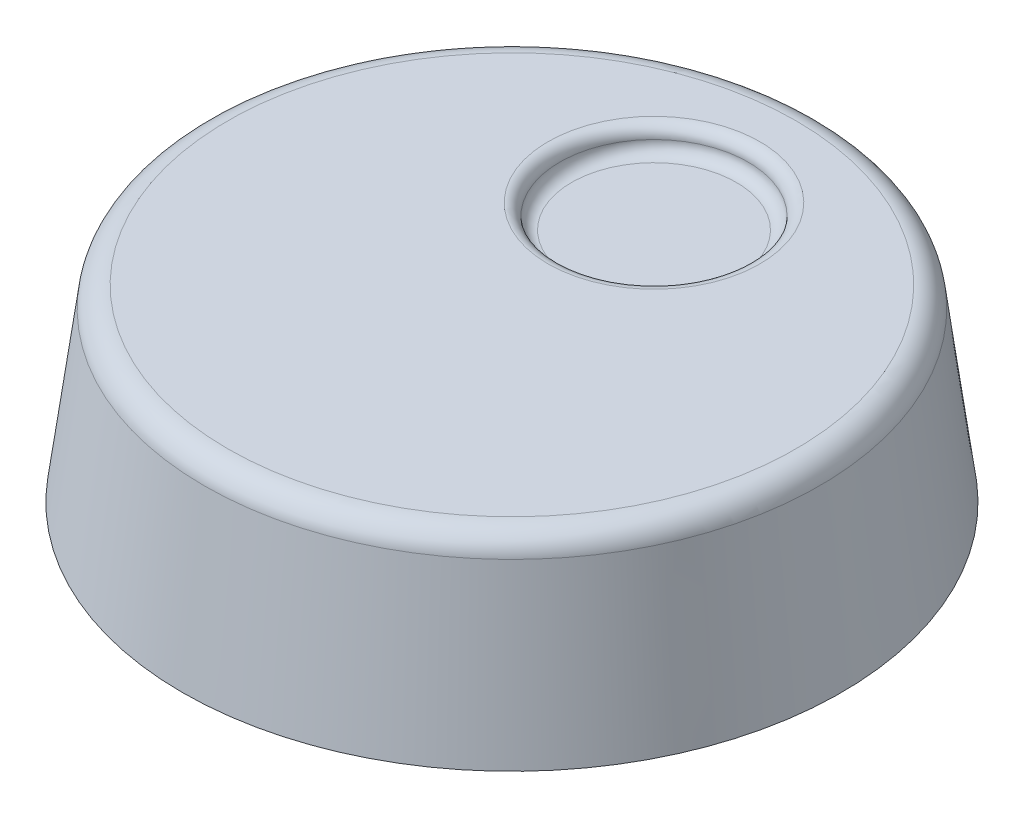
SolidWorks part; units mm, degrees
ref_plane "Front Plane" through (0, 0, 0) normal (0, 0, 1) x (1, 0, 0)
ref_plane "Top Plane" through (0, 0, 0) normal (0, 1, 0) x (1, 0, 0)
ref_plane "Right Plane" through (0, 0, 0) normal (1, 0, 0) x (0, 0, -1)
sketch "Sketch1" plane through (0, 0, 0) normal (0, 1, 0) x (1, 0, 0)
  circle A0 centre (0, 0) radius 22.225
  dimension "D1" = 44.45
extrude "Boss-Extrude1" add sketch "Sketch1" along normal blind 12.7 draft 7.5
fillet "Fillet1" radius 1.5875 1 edges at (0, 12.7, 20.553)
sketch "Sketch2" plane through (0, 12.7, 0) normal (0, 1, 0) x (1, 0, 0)
  line L0 (0, 19.1608) -> (0, 0) construction
  circle A0 centre (0, 9.5804) radius 6.35
  circle A1 centre (0, 0) radius 19.1608 construction
  point P7 (0, 9.5804)
  dimension "D1" = 12.7
extrude "Cut-Extrude1" cut sketch "Sketch2" against normal blind 1.5875
fillet "Fillet2" radius 0.7937 2 edges at (0, 12.7, -3.2304) (0, 11.1125, -3.2304)
sketch "Sketch3" plane through (0, 0, 0) normal (0, -1, 0) x (1, 0, 0)
  line L0 (-3.175, 3.175) -> (3.175, 3.175) construction
  line L1 (-2.8511, -1.397) -> (2.8511, -1.397)
  arc A0 (2.8511, -1.397) -> (-2.8511, -1.397) centre (0, 0) ccw
  point P3 (0, 3.175)
  point P6 (0, 0)
  dimension "D1" = 6.35
  dimension "D2" = 6.35
  dimension "D3" = 4.572
extrude "Cut-Extrude2" cut sketch "Sketch3" against normal blind 9.525
sketch "Sketch4" plane through (0, 0, 0) normal (0, -1, 0) x (1, 0, 0)
  circle A0 centre (0, 0) radius 3.175
  arc A1 (2.8511, -1.397) -> (-2.8511, -1.397) centre (0, 0) ccw construction
extrude "Cut-Extrude3" cut sketch "Sketch4" against normal blind 2.54
